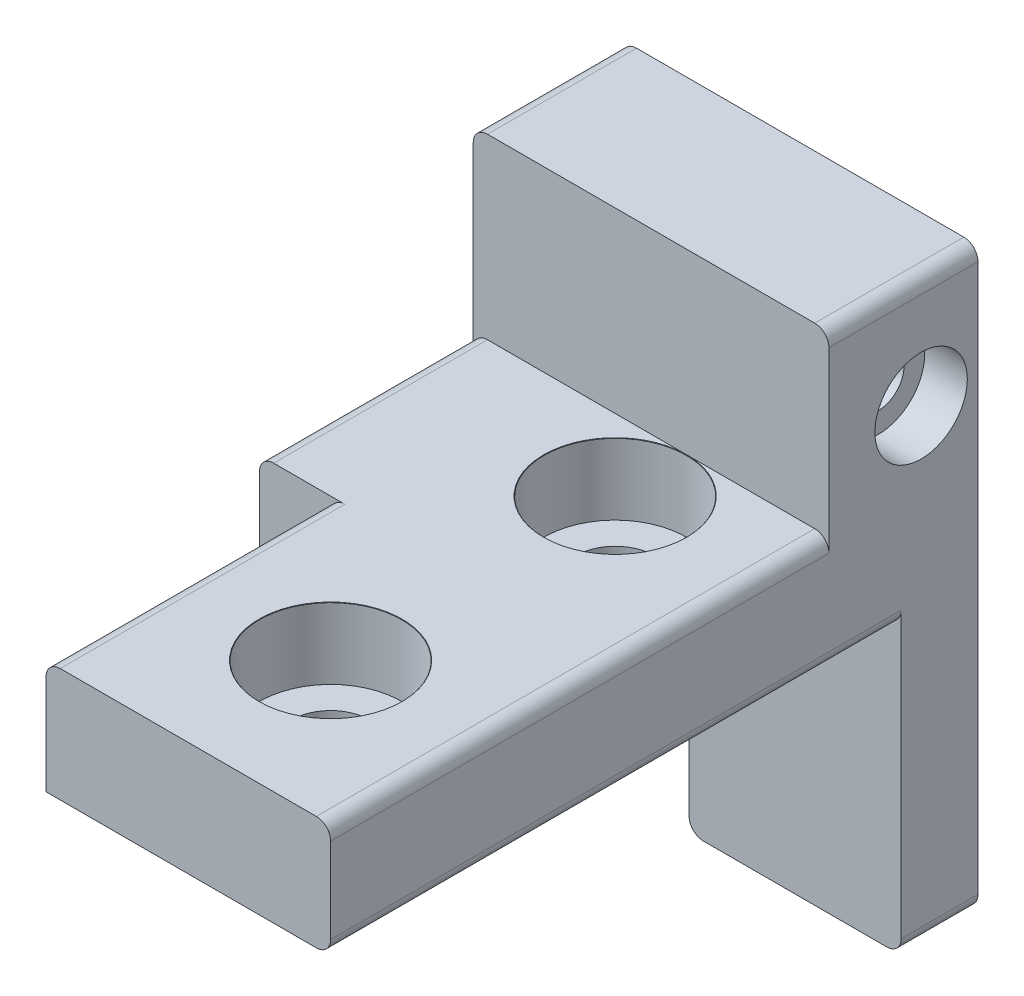
SolidWorks part; units mm, degrees
ref_plane "Front Plane" through (0, 0, 0) normal (0, 0, 1) x (1, 0, 0)
ref_plane "Top Plane" through (0, 0, 0) normal (0, 1, 0) x (1, 0, 0)
ref_plane "Right Plane" through (0, 0, 0) normal (1, 0, 0) x (0, 0, -1)
sketch "Sketch1" plane through (0, 0, 0) normal (0, 1, 0) x (1, 0, 0)
  line L0 (-10, 0) -> (-15, 0)
  line L1 (-10, -20) -> (10, -20)
  line L2 (-10, -20) -> (-10, 0)
  line L3 (-10, 20) -> (10, 20)
  line L4 (10, -20) -> (10, 20)
  line L5 (-10, -20) -> (10, 20) construction
  line L6 (-10, 20) -> (10, -20) construction
  line L7 (-15, 0) -> (-15, 20)
  line L8 (-15, 20) -> (-10, 20)
  point P0 (0, 0)
  dimension "D1" = 20
  dimension "D2" = 40
  dimension "D3" = 20
  dimension "D4" = 5
extrude "Boss-Extrude1" add sketch "Sketch1" along normal blind 8
sketch "Sketch2" plane through (0, 8, 0) normal (0, 1, 0) x (1, 0, 0)
  line L0 (0, -20) -> (0, 20) construction
  line L1 (-10, -20) -> (10, -20) construction
  line L2 (10, 20) -> (-15, 20) construction
  line L3 (-15, 10) -> (10, 10) construction
  line L4 (-15, 20) -> (-15, 0) construction
  line L5 (10, -20) -> (10, 20) construction
  point P14 (0, 10)
  point P15 (0, -10)
  dimension "D2" = 20
hole_wizard "CBORE for M5 SHCS1" positions "Sketch3" profile "Sketch4" counterbore size "M5" standard "ANSI Metric" end condition through all
sketch "Sketch3" plane through (0, 8, 0) normal (0, 1, 0) x (1, 0, 0)
  point P3 (0, 10)
  point P6 (0, -10)
sketch "Sketch4" plane through (0, 8, -10) normal (1, 0, 0) x (0, 0, 1)
  line L0 (0, 0) -> (0, 8)
  line L1 (0, 8) -> (2.75, 8)
  line L3 (2.75, 8) -> (2.75, 5)
  line L4 (5, 5) -> (2.75, 5)
  line L5 (5, 5) -> (5, 0.025)
  line L6 (5, 0.025) -> (5.025, 0)
  line L7 (5.025, 0) -> (0, 0)
  line L8 (-5, 0.025) -> (-5.025, 0) construction
  line L11 (0, -6.35) -> (0, 107.95) construction
  dimension "Thru Hole Dia." = 5.5
  dimension "Thru Hole Depth" = 8
  dimension "C'Bore Dia." = 10
  dimension "C'Bore Depth" = 5
  dimension "Near C'Sink Dia." = 10.05
  dimension "Near C'Sink Angle" = 90
sketch "Sketch5" plane through (0, 8, 0) normal (0, 1, 0) x (1, 0, 0)
  line L0 (10, -20) -> (10, 20) construction
  line L1 (-15, 18) -> (10, 18)
  line L2 (-15, 18) -> (-15, 15.025)
  line L3 (-15, 15.025) -> (10, 15.025)
  line L4 (10, 18) -> (10, 15.025)
  line L5 (10, 20) -> (-15, 20) construction
  line L6 (-15, 20) -> (-15, 0) construction
  circle A0 centre (0, 10) radius 5.025 construction
  dimension "D1" = 2
extrude "Boss-Extrude2" add sketch "Sketch5" along normal blind 12.51
sketch "Sketch6" plane through (0, 0, -18) normal (0, 0, -1) x (-1, 0, 0)
  line L0 (15, 20.51) -> (15, 8) construction
  line L1 (-10, 20.51) -> (15, 20.51)
  line L2 (-10, 20.51) -> (-10, 20)
  line L3 (-5, 17.51) -> (15, 17.51)
  line L4 (15, 20.51) -> (15, 17.51)
  line L5 (-5, 17.51) -> (-5, 8)
  line L6 (15, 8) -> (-10, 8) construction
  line L7 (-5, 8) -> (-10, 8)
  line L8 (-10, 8) -> (-10, 20)
  line L9 (15, 16.01) -> (12, 16.01)
  line L10 (12, 16.01) -> (12, 8)
  line L11 (-10, 8) -> (15, 8) construction
  line L12 (12, 8) -> (15, 8)
  line L13 (15, 8) -> (15, 16.01)
  dimension "D1" = 3
  dimension "D2" = 3
  dimension "D3" = 1.5
  dimension "D4" = 5
extrude "Boss-Extrude3" add sketch "Sketch6" along normal blind 7.5
sketch "Sketch7" plane through (0, 0, -20) normal (0, 0, -1) x (-1, 0, 0)
  line L6 (-10, 0) -> (15, 0)
  line L7 (15, 0) -> (15, 8)
  line L8 (15, 8) -> (12, 8)
  line L9 (12, 8) -> (-5, 8)
  line L10 (-5, 8) -> (-10, 8)
  line L11 (-10, 8) -> (-10, 0)
  line L12 (-10, 0) -> (15, 0)
  line L13 (15, 0) -> (15, 8)
  line L14 (15, 8) -> (12, 8)
  line L15 (12, 8) -> (-5, 8)
  line L16 (-5, 8) -> (-10, 8)
  line L17 (-10, 8) -> (-10, 0)
  dimension "D1" = 0
extrude "Boss-Extrude4" add sketch "Sketch7" along normal up to surface (5.5 mm away) up to face at (0, 15.34, -25.5)
sketch "Sketch8" plane through (0, 0, -18) normal (0, 0, -1) x (-1, 0, 0)
  line L0 (12, 16.01) -> (12, 8) construction
  line L1 (-5, 8) -> (12, 8)
  line L2 (-5, 8) -> (-5, 9.25)
  line L3 (-5, 9.25) -> (12, 9.25)
  line L4 (12, 8) -> (12, 9.25)
  dimension "D1" = 1.25
extrude "Boss-Extrude5" add sketch "Sketch8" along normal up to surface (7.5 mm away) up to face at (-5.4, 12.406, -25.5)
sketch "Sketch9" plane through (0, 0, -25.5) normal (0, 0, -1) x (-1, 0, 0)
  line L0 (-10, 0) -> (15, 0)
  line L1 (15, 0) -> (15, -5.4)
  line L2 (15, -5.4) -> (4.9, -5.4)
  line L3 (4.9, -5.4) -> (4.9, -20)
  line L4 (4.9, -20) -> (-10, -20)
  line L5 (-10, -20) -> (-10, 0)
  dimension "D1" = 5.4
  dimension "D2" = 10.1
  dimension "D3" = 20
extrude "Boss-Extrude6" add sketch "Sketch9" against normal blind 5.4
fillet "Fillet2" radius 1 10 edges at (-15, 0, -10.05) (10, 0, -0.05) (-10, 8, 10) (-15, 8, -7.5125) (10, 8, 2.4875) (-15, 20.51, -20.2625) (10, 20.51, -20.2625) (-15, -5.4, -22.8) (-4.9, -20, -22.8) (10, -20, -22.8)
sketch "Sketch10" plane through (10, 0, 0) normal (1, 0, 0) x (0, 0, -1)
  circle A0 centre (21.5, 12.75) radius 2.35 construction
  circle A1 centre (21.5, 12.75) radius 2.35
hole_wizard "CBORE for M3 SHCS1" positions "Sketch11" profile "Sketch12" counterbore size "M3" standard "ANSI Metric" end condition up to next
sketch "Sketch11" plane through (10, 0, 0) normal (1, 0, 0) x (0, 0, -1)
  point P0 (21.5, 12.75)
sketch "Sketch12" plane through (10, 12.75, -21.5) normal (0, 1, 0) x (0, 0, -1)
  line L0 (0, 0) -> (0, 5)
  line L1 (0, 5) -> (1.8, 5)
  line L3 (1.8, 5) -> (1.8, 3)
  line L4 (1.8, 3) -> (3.25, 3)
  line L5 (3.25, 3) -> (3.25, 0)
  line L7 (3.25, 0) -> (0, 0)
  line L11 (0, -6.35) -> (0, 107.95) construction
  dimension "Thru Hole Dia." = 3.6
  dimension "Thru Hole Depth" = 5
  dimension "C'Bore Dia." = 6.5
  dimension "C'Bore Depth" = 3
sketch "Sketch13" plane through (0, 0, -25.5) normal (0, 0, -1) x (-1, 0, 0)
  line L0 (-10, 7) -> (-10, 1) construction
  line L1 (-10, 7) -> (-10, 1) construction
  line L2 (-10, 4) -> (15, 4) construction
  line L3 (15, -4.4) -> (15, 16.01) construction
  line L4 (2.5, 20.51) -> (2.5, -20) construction
  line L5 (14, 20.51) -> (-9, 20.51) construction
  line L6 (-9, -20) -> (3.9, -20) construction
  circle A0 centre (10, 4) radius 2.4
  circle A1 centre (-5, 4) radius 2.4
  point P6 (10, 4)
  point P7 (-5, 4)
  point P14 (2.5, 4)
  dimension "D3" = 4.8
  dimension "D1" = 15
  dimension "D2" = 7.5
extrude "Cut-Extrude1" cut sketch "Sketch13" against normal blind 3.8
sketch "Sketch14" plane through (0, 0, -21.7) normal (0, 0, -1) x (-1, 0, 0)
  circle A0 centre (-5, 4) radius 1.65
  circle A1 centre (10, 4) radius 1.65
  dimension "D1" = 3.3
extrude "Cut-Extrude2" cut sketch "Sketch14" against normal blind 3
